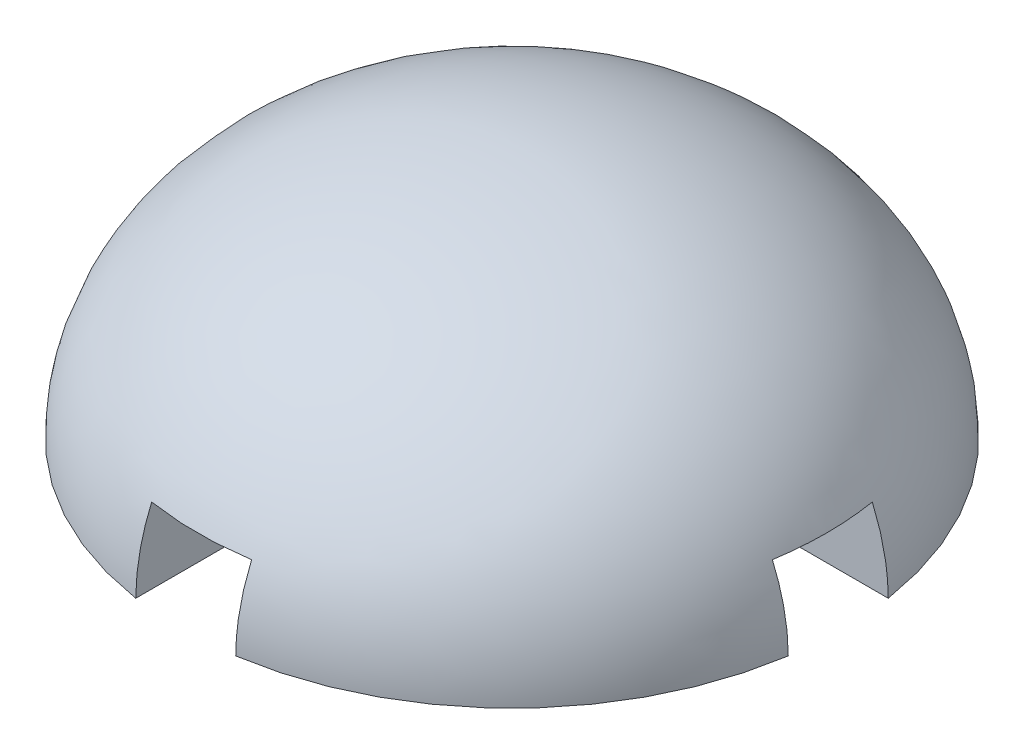
SolidWorks part; units mm, degrees
ref_plane "Front Plane" through (0, 0, 0) normal (0, 0, 1) x (1, 0, 0)
ref_plane "Top Plane" through (0, 0, 0) normal (0, 1, 0) x (1, 0, 0)
ref_plane "Right Plane" through (0, 0, 0) normal (1, 0, 0) x (0, 0, -1)
sketch "Sketch2" plane through (0, 0, 0) normal (0, 0, 1) x (1, 0, 0)
  line L0 (0, 0) -> (0, 17.5)
  line L2 (17.5, 0) -> (0, 0)
  arc A0 (17.5, 0) -> (0, 17.5) centre (0, 0) ccw
  dimension "D1" = 35
revolve "Revolve1" add sketch "Sketch2" angle 360 about L0
scale "Scale1" scale about centroid uniform scaling no x scale factor 1 y scale factor 0.75 z scale factor 1
ref_axis "Axis1" through (0, 0.9844, 0) along (0, 1, 0)
sketch "Sketch3" plane through (0, 0, 0) normal (0, 0, 1) x (1, 0, 0)
  line L2 (-2.65, 5.6406) -> (2.65, 5.6406)
  line L4 (-2.65, 5.6406) -> (2.65, 5.6406) construction
  line L9 (-2.65, 5.6406) -> (2.65, 5.6406) construction
  line L22 (-2.65, 5.6406) -> (2.65, 5.6406) construction
  line L23 (-2.65, 5.6406) -> (-2.65, 1.6406)
  line L25 (2.65, 5.6406) -> (2.65, 1.6406)
  line L26 (-2.65, 1.6406) -> (-0.2355, 1.6406) construction
  line L28 (0.165, 1.6406) -> (2.65, 1.6406) construction
  line L29 (-2.65, 1.6406) -> (2.65, 1.6406)
extrude "Cut-Extrude1" cut sketch "Sketch3" along normal mid plane 35
pattern_circular "CirPattern1" count 2 every 90 about axis through (0, 0.9844, 0) along (0, 1, 0) of "Cut-Extrude1"
sketch "Sketch4" plane through (0, 5.6406, 0) normal (0, -1, 0) x (1, 0, 0)
  circle A0 centre (0, 0) radius 1
  circle A1 centre (0, 0) radius 2.5
extrude "Boss-Extrude1" add sketch "Sketch4" along normal up to surface (4 mm away) up to face at (8.3328, 1.6406, -8.3328)
sketch "Sketch5" plane through (0, 5.6406, 0) normal (0, -1, 0) x (1, 0, 0)
  circle A0 centre (0, 0) radius 1
extrude "Cut-Extrude2" cut sketch "Sketch5" against normal blind 7.5
